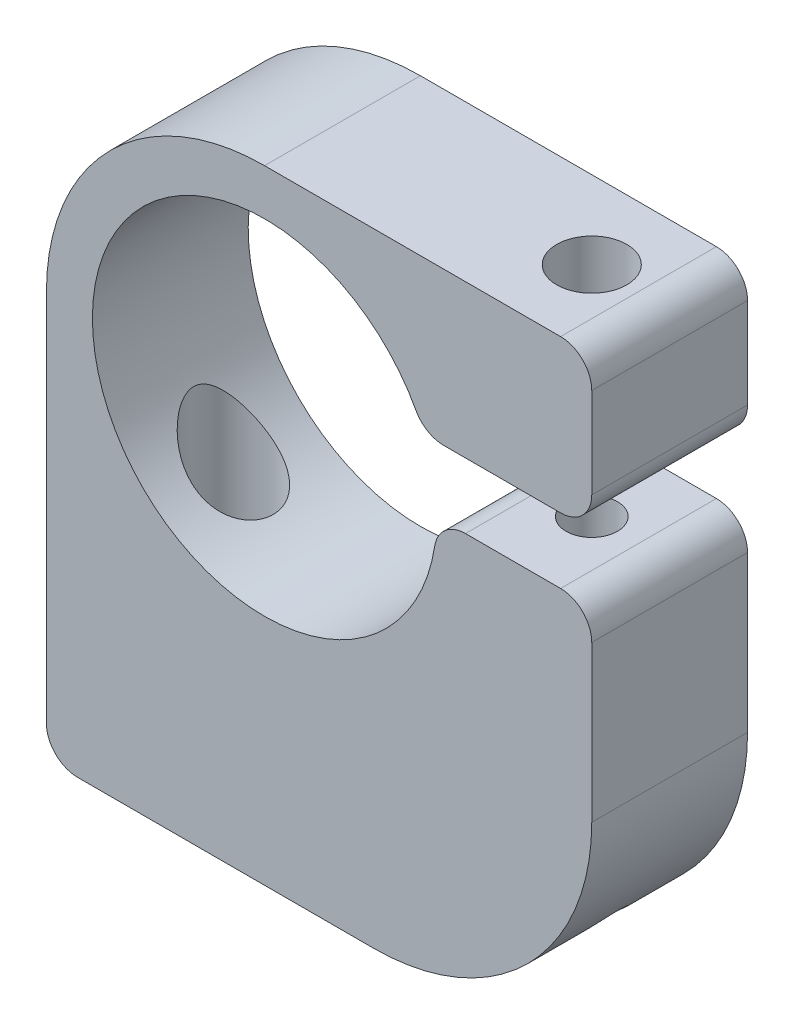
SolidWorks part; units mm, degrees
material "Сплав 2024"
ref_plane "Спереди" through (0, 0, 0) normal (0, 0, 1) x (1, 0, 0)
ref_plane "Сверху" through (0, 0, 0) normal (0, 1, 0) x (1, 0, 0)
ref_plane "Справа" through (0, 0, 0) normal (1, 0, 0) x (0, 0, -1)
sketch "Эскиз1" plane through (0, 0, 0) normal (0, 0, 1) x (1, 0, 0)
  line L0 (10.2207, 4.2) -> (21, 4.2)
  line L1 (0, 14) -> (21, 14)
  line L2 (-14, 0) -> (-14, -26)
  line L3 (-14, -26) -> (7, -26)
  line L4 (21, 14) -> (21, 4.2)
  line L5 (21, 0) -> (11.05, 0)
  line L6 (21, 0) -> (21, -12)
  arc A0 (10.2207, 4.2) -> (11.05, 0) centre (0, 0) ccw
  arc A1 (0, 14) -> (-14, 0) centre (0, 0) ccw
  arc A2 (7, -26) -> (21, -12) centre (7, -12) ccw
  dimension "D1" = 22.1
  dimension "D2" = 28
  dimension "D7" = 28
  dimension "D3" = 35
  dimension "D4" = 4.2
  dimension "D5" = 9.8
  dimension "D6" = 26
extrude "Бобышка-Вытянуть1" add sketch "Эскиз1" along normal blind 10
sketch "Эскиз2" plane through (0, 14, 0) normal (0, 1, 0) x (1, 0, 0)
  line L0 (21, -5) -> (1.7357, -5) construction
  line L1 (21, -10) -> (21, 0) construction
  line L2 (16, 0) -> (16, -10) construction
  line L3 (21, 0) -> (0, 0) construction
  line L4 (21, -10) -> (0, -10) construction
  dimension "D1" = 5
hole_wizard "Отверстие с зазором M41" positions "Эскиз4" profile "Эскиз3" hole size "M4" standard "Ansi Metric" end condition up to next
sketch "Эскиз4" plane through (0, 14, 0) normal (0, 1, 0) x (1, 0, 0)
  line L0 (16, 0) -> (16, -10) construction
  point P0 (16, -5)
sketch "Эскиз3" plane through (16, 14, 5) normal (1, 0, 0) x (0, 0, 1)
  line L0 (0, 0) -> (0, 9.8)
  line L1 (0, 9.8) -> (2.25, 9.8)
  line L2 (2.25, 9.8) -> (2.25, 0)
  line L5 (2.25, 0) -> (0, 0)
  line L11 (0, -6.35) -> (0, 107.95) construction
  dimension "Диаметр сквозного отверстия" = 4.5
  dimension "Глубина сквозного отверстия" = 9.8
hole_wizard "Отверстие обработанное метчиком M4x0.71" positions "Эскиз6" profile "Эскиз5" tap size "M4x0.7" standard "Ansi Metric" end condition through all
sketch "Эскиз6" plane through (0, 0, 0) normal (0, 1, 0) x (1, 0, 0)
  line L0 (16, 0) -> (16, -10) construction
  point P0 (16, -5)
sketch "Эскиз5" plane through (16, 0, 5) normal (1, 0, 0) x (0, 0, 1)
  line L0 (0, 0) -> (0, 26)
  line L1 (0, 26) -> (1.65, 26)
  line L2 (1.65, 26) -> (1.65, 0)
  line L5 (1.65, 0) -> (0, 0)
  line L11 (0, -6.35) -> (0, 107.95) construction
  dimension "Диаметр проходного сверла" = 3.3
  dimension "Глубина проходного сверла" = 26
cosmetic thread "Отверстие резьбы1" parameters "D2"=4
sketch "Эскиз7" plane through (0, -26, 0) normal (0, -1, 0) x (1, 0, 0)
  line L0 (-14, 5) -> (0, 5) construction
  line L1 (-14, 10) -> (-14, 0) construction
  line L2 (-7, 10) -> (-7, 0) construction
  line L3 (-14, 10) -> (7, 10) construction
  line L4 (-14, 0) -> (7, 0) construction
  dimension "D1" = 7
hole_wizard "Отверстие обработанное метчиком 1/4-201" positions "Эскиз9" profile "Эскиз8" tap size "1/4-20" standard "Ansi Inch" end condition up to next
sketch "Эскиз9" plane through (0, -26, 0) normal (0, -1, 0) x (-1, 0, 0)
  line L0 (14, -5) -> (0, -5) construction
  point P0 (7, -5)
sketch "Эскиз8" plane through (-7, -26, 5) normal (1, 0, 0) x (0, 0, -1)
  line L0 (0, 0) -> (0, 17.45)
  line L1 (0, 17.45) -> (2.5527, 17.45)
  line L2 (2.5527, 17.45) -> (2.5527, 0)
  line L5 (2.5527, 0) -> (0, 0)
  line L11 (0, -6.35) -> (0, 107.95) construction
  dimension "Диаметр проходного сверла" = 5.1054
  dimension "Глубина проходного сверла" = 17.45
cosmetic thread "Отверстие резьбы2" parameters "D2"=6.35
fillet "Скругление1" radius 2 6 edges at (-14, -26, 5) (21, 14, 5) (21, 4.2, 5) (21, 0, 5) (11.05, 0, 5) (10.2207, 4.2, 5)
fillet "Скругление2" [suppressed] radius 0.5
fillet "Скругление3" [suppressed] radius 0.5
sketch "Эскиз10" plane through (0, 0, 0) normal (0, 0, 1) x (1, 0, 0)
  line L0 (-12, -26) -> (7, -26) construction
  line L1 (-14, 0) -> (-14, -24) construction
  point P0 (-14, -26)
